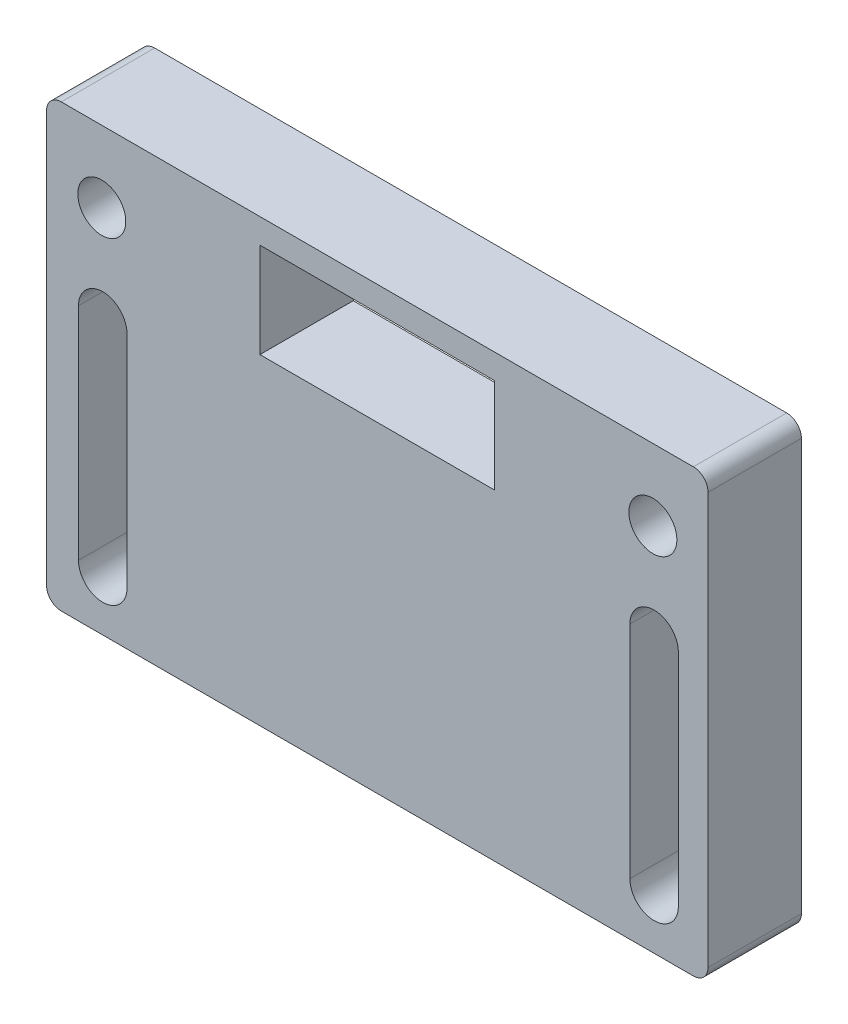
SolidWorks part; units mm, degrees
ref_plane "Front Plane" through (0, 0, 0) normal (0, 0, 1) x (1, 0, 0)
ref_plane "Top Plane" through (0, 0, 0) normal (0, 1, 0) x (1, 0, 0)
ref_plane "Right Plane" through (0, 0, 0) normal (1, 0, 0) x (0, 0, -1)
sketch "Sketch1" plane through (0, 0, 0) normal (0, 0, 1) x (1, 0, 0)
  line L0 (45, 0) -> (45, -60) construction
  line L1 (0, 0) -> (90, 0)
  line L2 (0, 0) -> (0, -60)
  line L3 (0, -60) -> (90, -60)
  line L4 (90, 0) -> (90, -60)
  line L5 (29.025, -3.3671) -> (29.025, -16.2671)
  line L6 (29.025, -16.2671) -> (60.975, -16.2671)
  line L7 (60.975, -16.2671) -> (60.975, -3.3671)
  line L9 (60.975, -3.3671) -> (45, -3.3671)
  line L10 (45, -3.3671) -> (29.025, -3.3671)
  dimension "D1" = 90
  dimension "D2" = 60
  dimension "D3" = 31.95
  dimension "D4" = 12.9
extrude "Boss-Extrude1" add sketch "Sketch1" along normal blind 12.7
sketch "Sketch2" plane through (0, 0, 0) normal (0, 0, -1) x (-1, 0, 0)
  line L0 (-82.49, -9.7171) -> (-7.51, -9.7171) construction
  line L1 (0, -9.7171) -> (-7.51, -9.7171)
  line L2 (-90, -60) -> (-90, 0) construction
  line L3 (-90, -9.7171) -> (-82.49, -9.7171)
  line L4 (0, 0) -> (0, -60) construction
  dimension "D1" = 7.51
  dimension "D2" = 7.51
  dimension "D3" = 74.98
hole_wizard "CSK for 1/4 Flat Head Machine Screw1" positions "Sketch3" profile "Sketch4" countersink size "1/4" standard "ANSI Inch" end condition through all
sketch "Sketch3" plane through (0, 0, 0) normal (0, 0, -1) x (-1, 0, 0)
  point P0 (-82.49, -9.7171)
  point P3 (-7.51, -9.7171)
sketch "Sketch4" plane through (82.49, -9.7171, 0) normal (1, 0, 0) x (0, 1, 0)
  line L0 (0, 0) -> (0, 12.7)
  line L1 (0, 12.7) -> (3.2639, 12.7)
  line L2 (3.2639, 12.7) -> (3.2639, 3.6524)
  line L3 (3.2639, 3.6524) -> (6.4389, 0)
  line L5 (6.4389, 0) -> (0, 0)
  line L6 (-3.2639, 3.6524) -> (-6.4389, 0) construction
  line L11 (0, -6.35) -> (0, 107.95) construction
  dimension "Thru Hole Dia." = 6.5278
  dimension "Thru Hole Depth" = 12.7
  dimension "Near C'Sink Dia." = 12.8778
  dimension "Near C'Sink Angle" = 82
fillet "Fillet1" radius 2 4 edges at (0, -60, 6.35) (0, 0, 6.35) (90, 0, 6.35) (90, -60, 6.35)
sketch "Sketch5" plane through (0, 0, 0) normal (0, 0, -1) x (-1, 0, 0)
  line L0 (-10.9392, -22.8474) -> (-10.9392, -52.8474)
  line L1 (-4.3392, -52.8474) -> (-4.3392, -22.8474)
  line L2 (-10.9392, -52.8474) -> (-79.3592, -52.8474) construction
  line L3 (-79.3592, -52.8474) -> (-79.3592, -22.8474)
  line L4 (-85.9592, -52.8474) -> (-85.9592, -22.8474)
  line L5 (0, -2) -> (0, -58) construction
  line L6 (-2, -60) -> (-88, -60) construction
  arc A0 (-10.9392, -52.8474) -> (-4.3392, -52.8474) centre (-7.6392, -52.8474) ccw
  arc A1 (-4.3392, -22.8474) -> (-10.9392, -22.8474) centre (-7.6392, -22.8474) ccw
  arc A2 (-85.9592, -52.8474) -> (-79.3592, -52.8474) centre (-82.6592, -52.8474) ccw
  arc A3 (-79.3592, -22.8474) -> (-85.9592, -22.8474) centre (-82.6592, -22.8474) ccw
  point P13 (0, 0)
  point P14 (-7.9333, -42.0456)
  point P15 (-10.5334, -52.2597)
  dimension "D1" = 3.3
  dimension "D4" = 3.3
  dimension "D7" = 7.1526
  dimension "D2" = 30
  dimension "D3" = 68.42
  dimension "D5" = 30
  dimension "D6" = 4.3392
extrude "Cut-Extrude1" cut sketch "Sketch5" against normal through all
